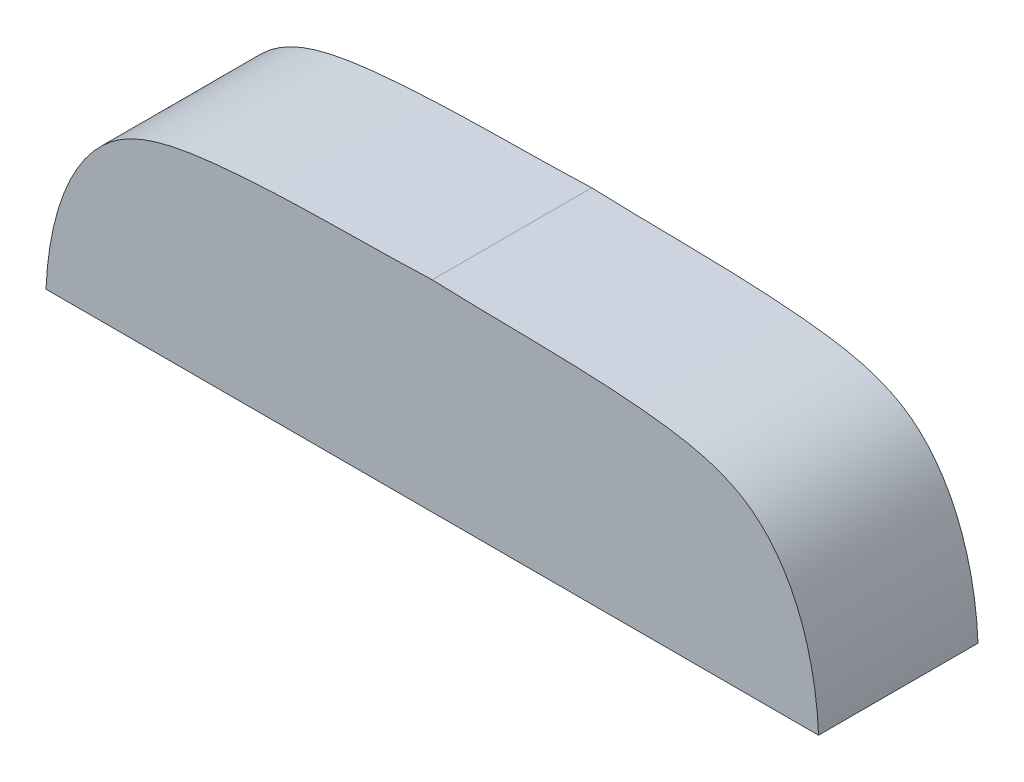
SolidWorks part; units mm, degrees
ref_plane "Front Plane" through (0, 0, 0) normal (0, 0, 1) x (1, 0, 0)
ref_plane "Top Plane" through (0, 0, 0) normal (0, 1, 0) x (1, 0, 0)
ref_plane "Right Plane" through (0, 0, 0) normal (1, 0, 0) x (0, 0, -1)
sketch "Sketch1" plane through (0, 0, 0) normal (0, 0, 1) x (1, 0, 0)
  line L2 (0, 265.0008) -> (0, -43.3016) construction
  line L3 (0, 55.9438) -> (-338.4201, 55.9438)
  line L4 (0, 55.9438) -> (338.4201, 55.9438)
  spline S0 degree 3 poles (0, 232.2583) (56.542, 229.7411) (174.4852, 232.8745) (302.7669, 203.9039) (335.8263, 117.8615) (338.4201, 55.9438) knots 0 0 0 0 0.225226 0.33784 0.524743 0.524743 0.524743 0.524743
  spline S1 degree 3 poles (0, 232.2583) (-56.542, 229.7411) (-174.4852, 232.8745) (-302.7669, 203.9039) (-335.8263, 117.8615) (-338.4201, 55.9438) knots 0 0 0 0 0.225226 0.33784 0.524743 0.524743 0.524743 0.524743
  point P8 (0, 0.0638)
  dimension "D2" = 55.88
extrude "Boss-Extrude1" add sketch "Sketch1" along normal blind 69.85 and the other way blind 69.85
